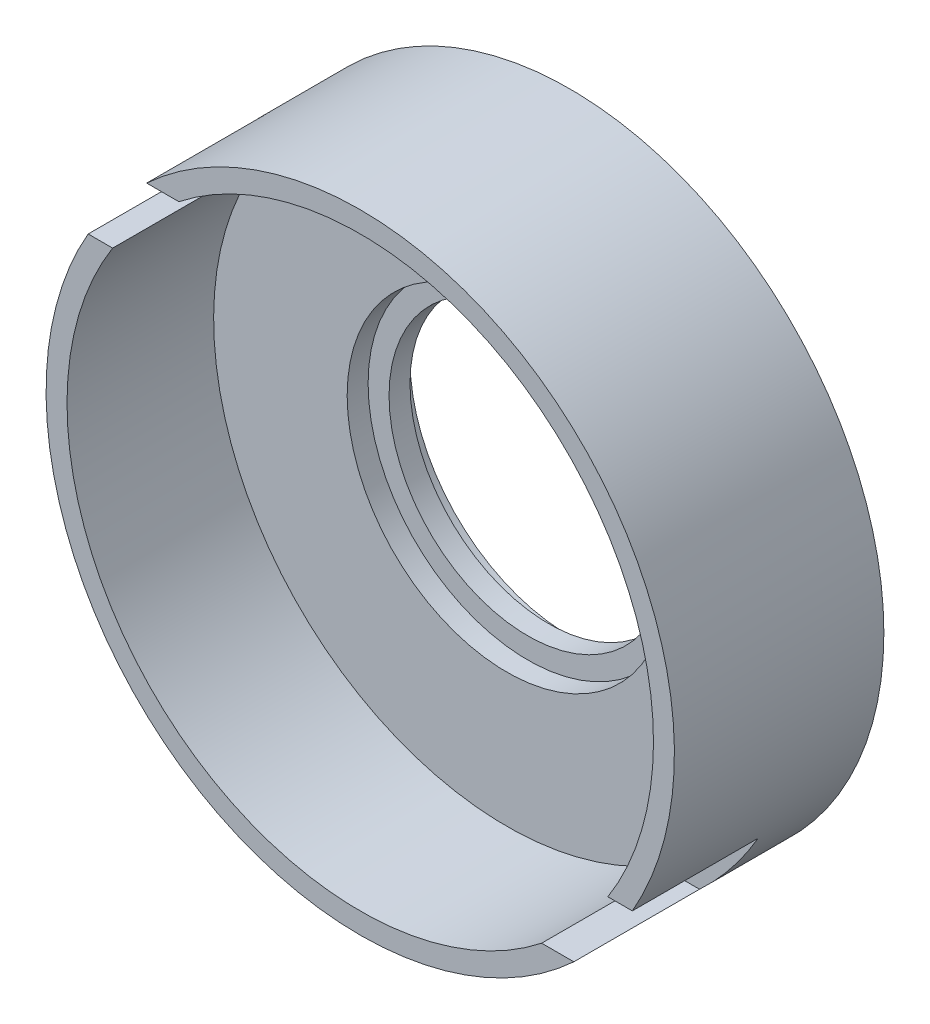
SolidWorks part; units mm, degrees
ref_plane "Спереди" through (0, 0, 0) normal (0, 0, 1) x (1, 0, 0)
ref_plane "Сверху" through (0, 0, 0) normal (0, 1, 0) x (1, 0, 0)
ref_plane "Справа" through (0, 0, 0) normal (1, 0, 0) x (0, 0, -1)
sketch "Эскиз5" plane through (0, 0, 0) normal (0, 0, 1) x (1, 0, 0)
  circle A0 centre (0, 0) radius 30
  dimension "D1" = 60
extrude "Бобышка-Вытянуть1" add sketch "Эскиз5" along normal blind 20
sketch "Эскиз6" plane through (0, 0, 0) normal (0, 0, 1) x (1, 0, 0)
  circle A0 centre (0, 0) radius 28
  dimension "D1" = 56
extrude "Вырез-Вытянуть1" cut sketch "Эскиз6" along normal blind 14 from offset 6
sketch "Эскиз7" plane through (0, 0, 0) normal (0, 0, 1) x (1, 0, 0)
  circle A0 centre (0, 0) radius 13.25
  dimension "D1" = 26.5
extrude "Вырез-Вытянуть2" cut sketch "Эскиз7" along normal blind 15
sketch "Эскиз8" plane through (0, 0, 0) normal (0, 0, 1) x (1, 0, 0)
  circle A0 centre (0, 0) radius 15.25
  dimension "D1" = 30.5
extrude "Вырез-Вытянуть3" cut sketch "Эскиз8" along normal blind 16 from offset 4
sketch "Эскиз10" plane through (0, 0, 0) normal (0, 0, 1) x (1, 0, 0)
  line L1 (-30, 15) -> (-15, 15)
  line L2 (-30, 15) -> (-30, 22)
  line L3 (-30, 22) -> (-15, 22)
  line L4 (-15, 15) -> (-15, 22)
  dimension "D1" = 15
  dimension "D2" = 15
  dimension "D3" = 7
  dimension "D4" = 15
extrude "Вырез-Вытянуть4" cut sketch "Эскиз10" along normal blind 12 from offset 8
sketch "Эскиз13" plane through (0, 0, 0) normal (0, 0, 1) x (1, 0, 0)
  line L1 (15, -15) -> (30, -15)
  line L2 (15, -15) -> (15, -22)
  line L3 (15, -22) -> (30, -22)
  line L4 (30, -15) -> (30, -22)
  dimension "D1" = 15
  dimension "D2" = 15
  dimension "D3" = 15
  dimension "D4" = 7
extrude "Вырез-Вытянуть5" cut sketch "Эскиз13" along normal blind 12 from offset 8
sketch "Эскиз14" plane through (0, 0, 0) normal (0, 0, 1) x (1, 0, 0)
  circle A0 centre (0, 0) radius 15.25
  dimension "D1" = 30.5
extrude "Вырез-Вытянуть6" cut sketch "Эскиз14" along normal blind 2
